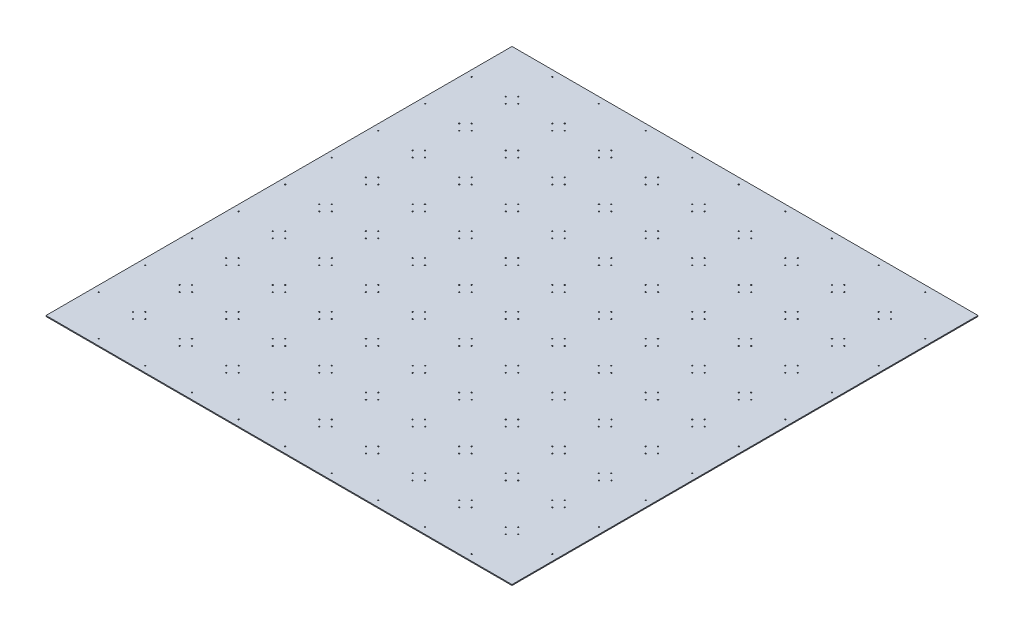
SolidWorks part; units mm, degrees
ref_plane "Front Plane" through (0, 0, 0) normal (0, 0, 1) x (1, 0, 0)
ref_plane "Top Plane" through (0, 0, 0) normal (0, 1, 0) x (1, 0, 0)
ref_plane "Right Plane" through (0, 0, 0) normal (1, 0, 0) x (0, 0, -1)
sketch "Sketch1" plane through (0, 0, 0) normal (0, 1, 0) x (1, 0, 0)
  line L1 (-1500, 1500) -> (1500, 1500)
  line L2 (-1500, 1500) -> (-1500, -1500)
  line L3 (-1500, -1500) -> (1500, -1500)
  line L4 (1500, 1500) -> (1500, -1500)
  line L5 (-1500, 1500) -> (1500, -1500) construction
  line L6 (-1500, -1500) -> (1500, 1500) construction
  point P0 (0, 0)
  dimension "D1" = 3000
  dimension "D2" = 3000
extrude "Boss-Extrude1" add sketch "Sketch1" along normal blind 6 contours L2 L3 L4 L1
sketch "Sketch2" plane through (0, 6, 0) normal (0, 1, 0) x (1, 0, 0)
  line L0 (-1500, -1500) -> (-1200, -1500) construction
  line L1 (-1500, -1500) -> (1500, -1500) construction
  line L2 (-1200, -1500) -> (-1200, -1200) construction
  circle A0 centre (-1200, -1240) radius 3.5
  circle A1 centre (-1200, -1460) radius 3.5
  point P5 (-1200, -1240)
  point P7 (-1200, -1460)
  dimension "D5" = 7
  dimension "D1" = 300
  dimension "D2" = 300
  dimension "D3" = 40
  dimension "D4" = 40
extrude "Cut-Extrude1" cut sketch "Sketch2" against normal through all contours A0 | A1 region at (-1200, 6, 1240)
pattern_linear "LPattern1" count 10 spacing 300 along (0, 0, -1) count 9 spacing 300 along (1, 0, 0) of "Cut-Extrude1"
sketch "Sketch3" plane through (0, 6, 0) normal (0, 1, 0) x (1, 0, 0)
  line L0 (-1500, -1500) -> (-1500, -1200) construction
  line L1 (-1500, 1500) -> (-1500, -1500) construction
  line L2 (-1500, -1200) -> (-1200, -1200) construction
  circle A0 centre (-1460, -1200) radius 3.5
  circle A1 centre (-1240, -1200) radius 3.5
  point P5 (-1460, -1200)
  point P7 (-1240, -1200)
  dimension "D5" = 7
  dimension "D1" = 300
  dimension "D2" = 300
  dimension "D3" = 40
  dimension "D4" = 40
extrude "Cut-Extrude2" cut sketch "Sketch3" against normal through all
pattern_linear "LPattern2" count 10 spacing 300 along (1, 0, 0) count 9 spacing 300 along (0, 0, -1) of "Cut-Extrude2"
